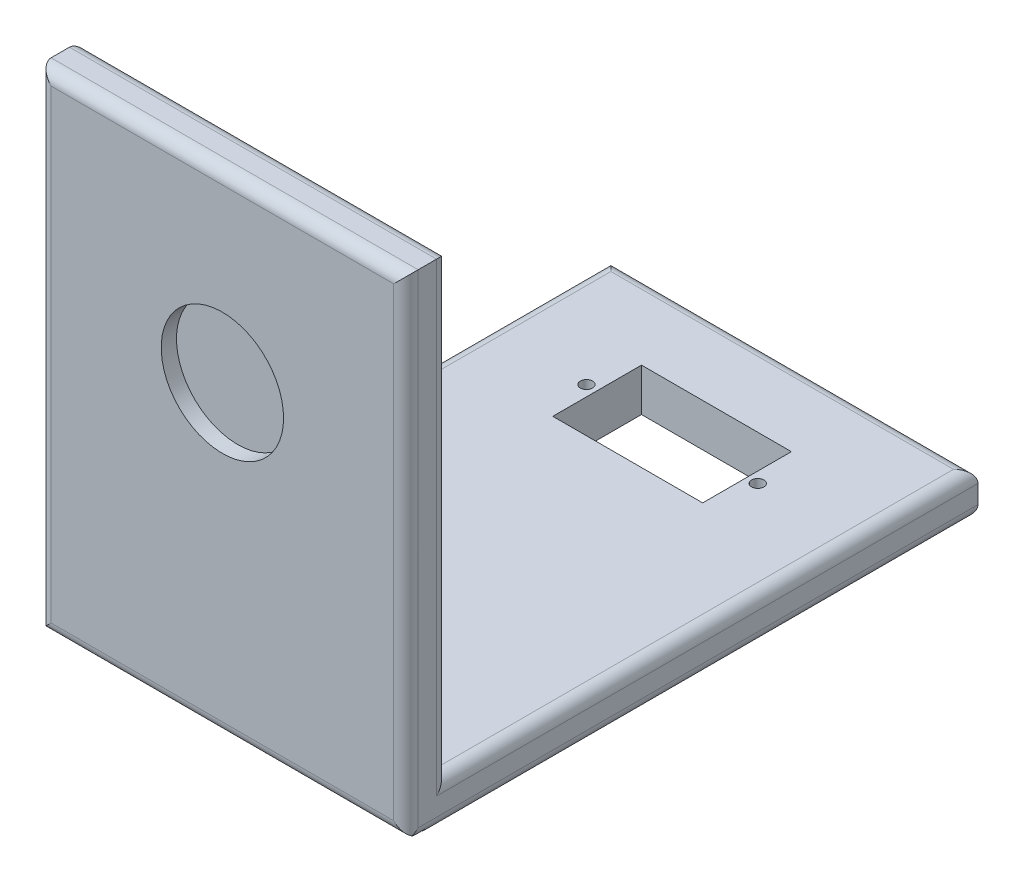
SolidWorks part; units mm, degrees
ref_plane "Alzado" through (0, 0, 0) normal (0, 0, 1) x (1, 0, 0)
ref_plane "Planta" through (0, 0, 0) normal (0, 1, 0) x (1, 0, 0)
ref_plane "Vista lateral" through (0, 0, 0) normal (1, 0, 0) x (0, 0, -1)
sketch "Croquis1" plane through (0, 0, 0) normal (0, 1, 0) x (1, 0, 0)
  line L0 (0, 0) -> (0, 40015.7255) construction
  line L1 (0, 0) -> (40015.7255, 0) construction
  line L3 (-30, -45) -> (30, -45)
  line L4 (-30, -45) -> (-30, 45)
  line L5 (-30, 45) -> (30, 45)
  line L6 (30, -45) -> (30, 45)
  line L7 (-30, -45) -> (30, 45) construction
  line L8 (-30, 45) -> (30, -45) construction
  point P5 (0, 0)
  dimension "D1" = 60
  dimension "D2" = 90
extrude "Base" add sketch "Croquis1" along normal blind 3.5 and the other way blind 3.5
sketch "Croquis2" plane through (0, 3.5, 0) normal (0, 1, 0) x (1, 0, 0)
  line L0 (0, 0) -> (0, 50000) construction
  line L1 (0, 0) -> (50000, 0) construction
  line L3 (-12.25, 17.75) -> (12.25, 17.75)
  line L4 (-12.25, 17.75) -> (-12.25, 32.25)
  line L5 (-12.25, 32.25) -> (12.25, 32.25)
  line L6 (12.25, 17.75) -> (12.25, 32.25)
  line L7 (-12.25, 17.75) -> (12.25, 32.25) construction
  line L8 (-12.25, 32.25) -> (12.25, 17.75) construction
  line L9 (30, 45) -> (-30, 45) construction
  circle A2 centre (-14, 25) radius 1
  circle A3 centre (14, 25) radius 1
  point P5 (0, 25)
  point P14 (0, 0)
  point P15 (0, 0)
  point P16 (0, 0)
  point P17 (0, 0)
  point P18 (0, 0)
  point P19 (0, 0)
  point P20 (0, 0)
  point P21 (0, 0)
  point P24 (0, 0)
  point P25 (0, 0)
  dimension "D3" = 2
  dimension "D4" = 14
  dimension "D1" = 24.5
  dimension "D2" = 14.5
  dimension "D5" = 20
extrude "Agujero Servo" cut sketch "Croquis2" against normal up to next
sketch "Croquis3" plane through (0, 0, 45) normal (0, 0, 1) x (1, 0, 0)
  line L0 (0, 0) -> (0, 50000) construction
  line L1 (0, 0) -> (50000, 0) construction
  line L2 (-30, -3.5) -> (-30, 3.5) construction
  line L3 (-30, -2.5) -> (30, -2.5)
  line L4 (-30, -2.5) -> (-30, 77.5)
  line L5 (-30, 77.5) -> (30, 77.5)
  line L6 (30, -2.5) -> (30, 77.5)
  line L7 (30, -3.5) -> (30, 3.5) construction
  dimension "D1" = 80
extrude "Pared" add sketch "Croquis3" along normal blind 3.5 and the other way blind 3.5
fillet "Redondeo2" radius 2 13 edges at (0, 77.5, 48.5) (30, 37.5, 48.5) (0, -2.5, 48.5) (-30, 37.5, 48.5) (-30, 40.5, 41.5) (30, 40.5, 41.5) (0, 77.5, 41.5) (30, -3.5, 0) (30, 3.5, -1.75) (0, -3.5, -45) (0, 3.5, -45) (-30, -3.5, 0) (-30, 3.5, -1.75)
sketch "Croquis4" plane through (0, 0, 48.5) normal (0, 0, 1) x (1, 0, 0)
  line L0 (0, 0) -> (0, 50000) construction
  line L2 (-30, 77.5) -> (30, 77.5) construction
  circle A0 centre (0, 47.5) radius 10
  dimension "D1" = 20
  dimension "D2" = 30
extrude "RecorteNuevoServo" cut sketch "Croquis4" against normal blind 2.5
